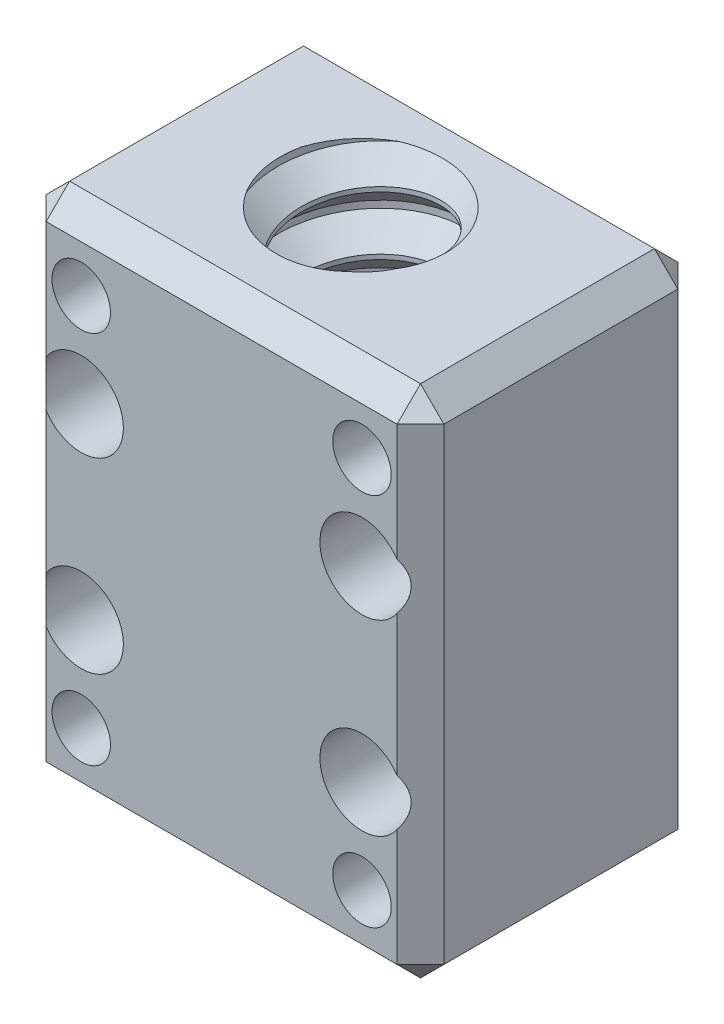
SolidWorks part; units mm, degrees
ref_plane "前视基准面" through (0, 0, 0) normal (0, 0, 1) x (1, 0, 0)
ref_plane "上视基准面" through (0, 0, 0) normal (0, 1, 0) x (1, 0, 0)
ref_plane "右视基准面" through (0, 0, 0) normal (1, 0, 0) x (0, 0, -1)
sketch "草图1" plane through (0, 0, 0) normal (0, 0, 1) x (1, 0, 0)
  line L1 (-8.5, -11) -> (8.5, -11)
  line L2 (-8.5, -11) -> (-8.5, 11)
  line L3 (-8.5, 11) -> (8.5, 11)
  line L4 (8.5, -11) -> (8.5, 11)
  line L5 (-8.5, -11) -> (8.5, 11) construction
  line L6 (-8.5, 11) -> (8.5, -11) construction
  point P0 (0, 0)
  dimension "D1" = 17
  dimension "D2" = 22
extrude "凸台-拉伸1" add sketch "草图1" along normal blind 12
sketch "草图2" plane through (0, -11, 0) normal (0, -1, 0) x (1, 0, 0)
  line L0 (-8.5, 6) -> (8.5, 6) construction
  line L1 (-8.5, 12) -> (-8.5, 0) construction
  line L2 (8.5, 12) -> (8.5, 0) construction
  line L3 (0, 0) -> (0, 12) construction
  line L4 (-8.5, 12) -> (8.5, 12) construction
  circle A0 centre (0, 6) radius 4
  dimension "D1" = 8
extrude "切除-拉伸1" cut sketch "草图2" against normal up to next
sketch "草图3" plane through (0, -11, 0) normal (0, -1, 0) x (1, 0, 0)
  circle A0 centre (0, 6) radius 4 construction
  circle A1 centre (0, 6) radius 4
curve "螺旋线/涡状线1" pitch 2.5 height 22.5 turns 9
sketch "草图6" plane through (0, 0, 0) normal (1, 0, 0) x (0, 0, -1)
  line L0 (-2, -8.8) -> (-2, -11)
  line L1 (-2, -11) -> (-3, -10)
  line L2 (-3, -10) -> (-3, -9.8)
  line L3 (-3, -9.8) -> (-2, -8.8)
  point P2 (-3, -9.9)
  point P5 (-2, -9.9)
  dimension "D1" = 2.2
  dimension "D2" = 1
  dimension "D3" = 45
sweep "扫描1" add profiles "草图6" path "螺旋线/涡状线1"
sketch "草图7" plane through (0, 11, 0) normal (0, 1, 0) x (1, 0, 0)
  circle A0 centre (0, -6) radius 15.4839
extrude "切除-拉伸3" cut sketch "草图7" along normal blind 30
sketch "草图8" plane through (0, 0, 12) normal (0, 0, 1) x (1, 0, 0)
  line L0 (-14.8745, 4) -> (15.9779, 4) construction
  line L1 (0, 6.1723) -> (0, -6.7506) construction
  line L2 (-2.9516, 0) -> (3.5387, 0) construction
  line L3 (0, -6.1723) -> (0, 6.7506) construction
  line L4 (-14.8745, -4) -> (15.9779, -4) construction
  circle A0 centre (6, 4) radius 1.1
  circle A1 centre (-6, 4) radius 1.1
  circle A2 centre (-6, -4) radius 1.1
  circle A3 centre (6, -4) radius 1.1
  dimension "D1" = 2.2
  dimension "D2" = 12
  dimension "D3" = 8
extrude "切除-拉伸4" cut sketch "草图8" against normal through all
sketch "草图9" plane through (0, 0, 12) normal (0, 0, 1) x (1, 0, 0)
  circle A0 centre (-6, 4) radius 1.8
  circle A1 centre (6, 4) radius 1.8
  circle A2 centre (6, -4) radius 1.8
  circle A3 centre (-6, -4) radius 1.8
  dimension "D1" = 3.6
  dimension "D2" = 3.6
  dimension "D3" = 3.6
  dimension "D4" = 3.6
extrude "切除-拉伸5" cut sketch "草图9" against normal blind 7
sketch "草图10" plane through (0, 0, 12) normal (0, 0, 1) x (1, 0, 0)
  line L0 (-9.8772, 0) -> (10.0907, 0) construction
  line L1 (0, 11.8176) -> (0, -11.5673) construction
  circle A0 centre (6, 8) radius 1.25
  circle A1 centre (-6, 8) radius 1.25
  circle A2 centre (6, -8) radius 1.25
  circle A3 centre (-6, -8) radius 1.25
  dimension "D1" = 2.5
  dimension "D2" = 8
  dimension "D3" = 6
extrude "切除-拉伸6" cut sketch "草图10" against normal blind 7
fillet "圆角1" radius 1 12 edges at (8.5, -11, 6) (8.5, 11, 6) (0, 11, 0) (0, -11, 0) (8.5, 0, 0) (0, -11, 12) (0, 11, 12) (8.5, 0, 12) (-8.5, 11, 6) (-8.5, 0, 12) (-8.5, -11, 6) (-8.5, 0, 0) profile chamfer
